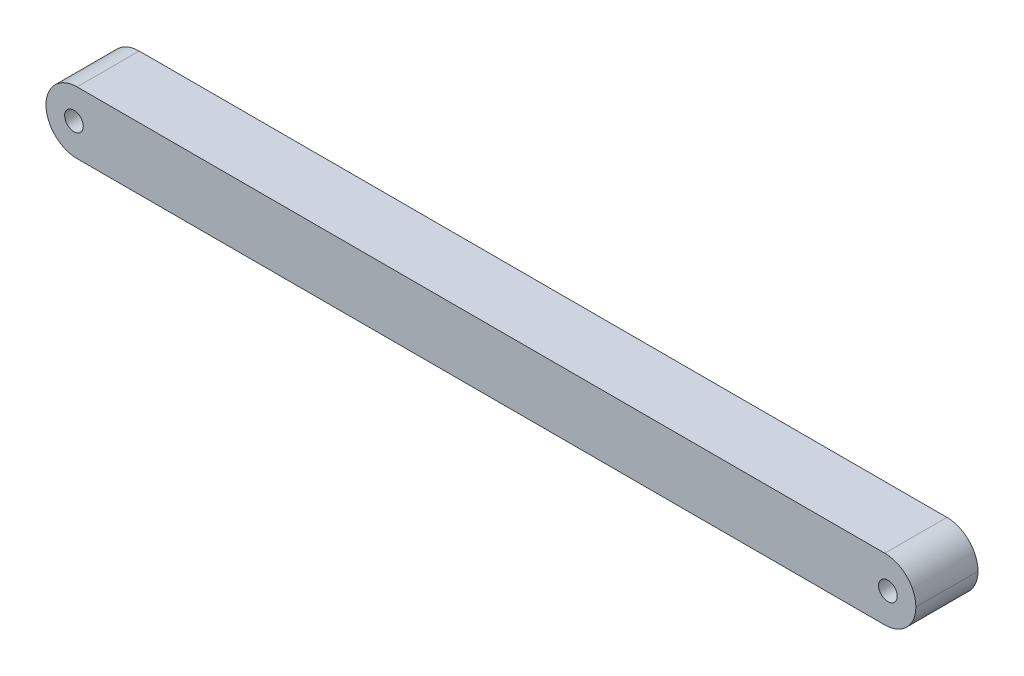
SolidWorks part; units mm, degrees
ref_plane "Front Plane" through (0, 0, 0) normal (0, 0, 1) x (1, 0, 0)
ref_plane "Top Plane" through (0, 0, 0) normal (0, 1, 0) x (1, 0, 0)
ref_plane "Right Plane" through (0, 0, 0) normal (1, 0, 0) x (0, 0, -1)
sketch "Sketch1" plane through (0, 0, 0) normal (0, 0, 1) x (1, 0, 0)
  line L0 (0, 5) -> (140, 5) construction
  line L1 (0, 0) -> (140, 0)
  line L2 (0, 0) -> (0, 10)
  line L3 (0, 10) -> (140, 10)
  line L4 (140, 0) -> (140, 10)
  line L5 (137, 5) -> (140, 5)
  line L6 (0, 5) -> (3, 5)
  circle A0 centre (4.5, 5) radius 1.5
  circle A1 centre (135.5, 5) radius 1.5
  dimension "D3" = 3
  dimension "D4" = 3
  dimension "D1" = 10
  dimension "D2" = 140
  dimension "D5" = 3
  dimension "D6" = 3
extrude "Boss-Extrude1" add sketch "Sketch1" along normal blind 10 contours A0 L0 A1 L5 L4 L3 L2 L6 | L0 A0 L6 L2 L1 L4 L5 A1 region at (70, 7.519, 0) region at (70, 2.481, 0)
fillet "Fillet1" radius 5 1 edges at (0, 10, 5) type face fillet first side face at (70, 10, 5) second side face at (0, 5, 5)
fillet "Fillet2" radius 5 1 edges at (0, 0, 5) type face fillet first side face at (0, 2.5, 5) second side face at (70, 0, 5)
fillet "Fillet3" radius 5 1 edges at (140, 10, 5) type face fillet first side face at (72.5, 10, 5) second side face at (140, 5, 5)
fillet "Fillet4" radius 5 1 edges at (140, 0, 5) type face fillet first side face at (72.5, 0, 5) second side face at (140, 2.5, 5)
